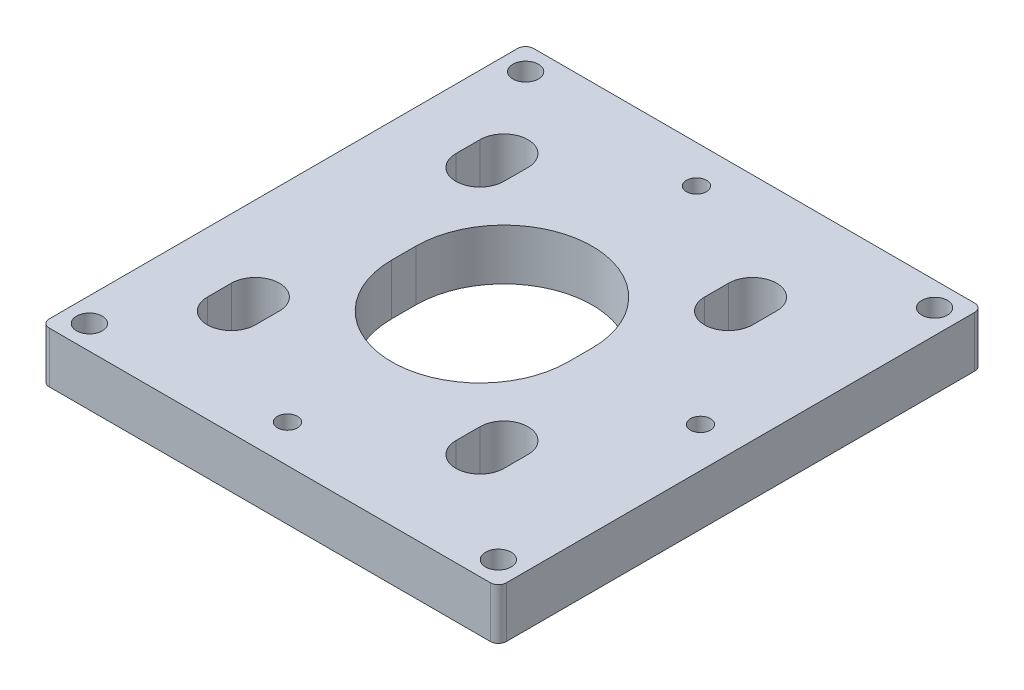
SolidWorks part; units mm, degrees
material "AISI 1045 Steel, cold drawn"
ref_plane "Front Plane" through (0, 0, 0) normal (0, 0, 1) x (1, 0, 0)
ref_plane "Top Plane" through (0, 0, 0) normal (0, 1, 0) x (1, 0, 0)
ref_plane "Right Plane" through (0, 0, 0) normal (1, 0, 0) x (0, 0, -1)
sketch "Sketch1" plane through (0, 0, 0) normal (0, 1, 0) x (1, 0, 0)
  line L0 (0, -1.5) -> (0, 1.5) construction
  line L1 (-11, -1.5) -> (-11, 1.5)
  line L2 (11, -1.5) -> (11, 1.5)
  line L3 (-15.5, 14) -> (-15.5, 17) construction
  line L4 (-18.5, 14) -> (-18.5, 17)
  line L5 (-12.5, 14) -> (-12.5, 17)
  line L6 (15.5, 14) -> (15.5, 17) construction
  line L7 (12.5, 14) -> (12.5, 17)
  line L8 (18.5, 14) -> (18.5, 17)
  line L9 (15.5, -17) -> (15.5, -14) construction
  line L10 (12.5, -17) -> (12.5, -14)
  line L11 (18.5, -17) -> (18.5, -14)
  line L12 (-15.5, -17) -> (-15.5, -14) construction
  line L13 (-18.5, -17) -> (-18.5, -14)
  line L14 (-12.5, -17) -> (-12.5, -14)
  line L15 (-15.5, 15.5) -> (15.5, 15.5) construction
  line L16 (-15.5, -15.5) -> (-15.5, 15.5) construction
  line L17 (21, -30.2) -> (21, 30.2) construction
  line L19 (-21, 30.2) -> (-21, -30.2) construction
  line L21 (31, 30.2) -> (31, -30.2)
  line L22 (-26, 30.2) -> (-26, -30.2)
  line L23 (31, 30.2) -> (-26, 30.2)
  line L24 (31, -30.2) -> (-26, -30.2)
  arc A0 (-11, -1.5) -> (11, -1.5) centre (0, -1.5) ccw
  arc A1 (11, 1.5) -> (-11, 1.5) centre (0, 1.5) ccw
  arc A2 (-18.5, 14) -> (-12.5, 14) centre (-15.5, 14) ccw
  arc A3 (-12.5, 17) -> (-18.5, 17) centre (-15.5, 17) ccw
  arc A4 (12.5, 14) -> (18.5, 14) centre (15.5, 14) ccw
  arc A5 (18.5, 17) -> (12.5, 17) centre (15.5, 17) ccw
  arc A6 (12.5, -17) -> (18.5, -17) centre (15.5, -17) ccw
  arc A7 (18.5, -14) -> (12.5, -14) centre (15.5, -14) ccw
  arc A8 (-18.5, -17) -> (-12.5, -17) centre (-15.5, -17) ccw
  arc A9 (-12.5, -14) -> (-18.5, -14) centre (-15.5, -14) ccw
  point P2 (0, 0)
  point P10 (-15.5, 15.5)
  point P16 (15.5, 15.5)
  point P23 (15.5, -15.5)
  point P30 (-15.5, -15.5)
  point P38 (0, 15.5)
  point P40 (-15.5, 0)
  point P43 (31, 0)
  point P50 (-21, -30.2)
  point P51 (-21, 30.2)
  point P52 (21, 30.2)
  point P53 (21, -30.2)
  dimension "D2" = 11
  dimension "D3" = 3
  dimension "D1" = 3
  dimension "D4" = 31
  dimension "D5" = 3
  dimension "D6" = 60.4
  dimension "D7" = 21
  dimension "D8" = 21
  dimension "D9" = 10
  dimension "D10" = 5
extrude "Boss-Extrude1" add sketch "Sketch1" along normal blind 6.35
hole_wizard "M3 Clearance Hole1" positions "Sketch2" profile "Sketch3" hole size "M3" standard "ANSI Metric" end condition through all
sketch "Sketch2" plane through (0, 6.35, 0) normal (0, 1, 0) x (1, 0, 0)
  line L2 (31, -30.2) -> (31, 30.2) construction
  line L4 (-26, -30.2) -> (31, -30.2) construction
  line L5 (-26, 30.2) -> (-26, -30.2) construction
  line L6 (31, 30.2) -> (-26, 30.2) construction
  point P0 (-23, -27.2)
  point P2 (28, -27.2)
  point P4 (28, 27.2)
  point P6 (-23, 27.2)
  point P28 (-17.8376, -30.2)
  dimension "D1" = 3
  dimension "D2" = 3
  dimension "D3" = 3
  dimension "D4" = 3
sketch "Sketch3" plane through (-23, 6.35, 27.2) normal (1, 0, 0) x (0, 0, 1)
  line L0 (0, 0) -> (0, 6.35)
  line L1 (0, 6.35) -> (1.6, 6.35)
  line L2 (1.6, 6.35) -> (1.6, 0)
  line L5 (1.6, 0) -> (0, 0)
  line L11 (0, -6.35) -> (0, 107.95) construction
  dimension "Thru Hole Dia." = 3.2
  dimension "Thru Hole Depth" = 6.35
hole_wizard "Tap Drill for M3x0.5 Tap1" positions "Sketch4" profile "Sketch5" hole size "M3x0.5" standard "ANSI Metric" end condition through all
sketch "Sketch4" plane through (0, 6.35, 0) normal (0, 1, 0) x (1, 0, 0)
  point P0 (26, 0)
  point P6 (0, 25.5)
  point P8 (0, -25.5)
  dimension "D1" = 26
  dimension "D2" = 25.5
  dimension "D3" = 25.5
sketch "Sketch5" plane through (26, 6.35, 0) normal (1, 0, 0) x (0, 0, 1)
  line L0 (0, 0) -> (0, 6.35)
  line L1 (0, 6.35) -> (1.25, 6.35)
  line L2 (1.25, 6.35) -> (1.25, 0)
  line L5 (1.25, 0) -> (0, 0)
  line L11 (0, -6.35) -> (0, 107.95) construction
  dimension "Thru Hole Dia." = 2.5
  dimension "Thru Hole Depth" = 6.35
fillet "Fillet1" radius 1 4 edges at (-26, 3.175, 30.2) (31, 3.175, -30.2) (31, 3.175, 30.2) (-26, 3.175, -30.2)
